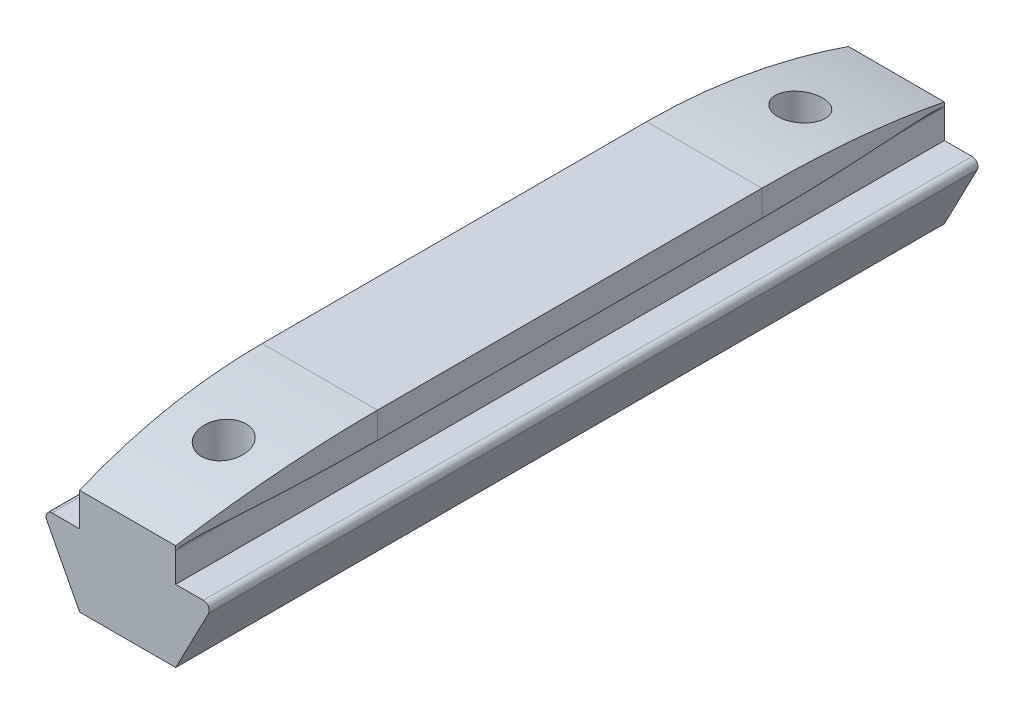
SolidWorks part; units mm, degrees
ref_plane "Front Plane" through (0, 0, 0) normal (0, 0, 1) x (1, 0, 0)
ref_plane "Top Plane" through (0, 0, 0) normal (0, 1, 0) x (1, 0, 0)
ref_plane "Right Plane" through (0, 0, 0) normal (1, 0, 0) x (0, 0, -1)
sketch "Sketch1" plane through (0, 0, 0) normal (0, 0, 1) x (1, 0, 0)
  line L0 (-5.6515, 0) -> (5.6515, 0)
  line L1 (5.6515, 0) -> (3.175, -4.7625)
  line L2 (3.175, -4.7625) -> (-3.175, -4.7625)
  line L3 (0, 0) -> (0, -5.9494) construction
  line L4 (-5.6515, 0) -> (-3.175, -4.7625)
  point P4 (0, -4.7625)
  dimension "D1" = 11.303
  dimension "D2" = 4.7625
  dimension "D3" = 6.35
extrude "Boss-Extrude1" add sketch "Sketch1" along normal mid plane 50.8
sketch "Sketch5" plane through (0, 0, 0) normal (0, 0, 1) x (1, 0, 0)
  line L0 (0, 0) -> (0, 5.1541) construction
  line L1 (5.6515, 0) -> (-5.6515, 0) construction
  line L2 (3.175, 0) -> (3.175, 2.2098)
  line L3 (3.175, 2.2098) -> (3.81, 2.2098)
  line L4 (3.81, 2.2098) -> (3.81, 3.937)
  line L5 (3.81, 3.937) -> (-3.81, 3.937)
  line L6 (3.175, 0) -> (-3.175, 0)
  line L7 (-3.81, 2.2098) -> (-3.81, 3.937)
  line L8 (-3.175, 2.2098) -> (-3.81, 2.2098)
  line L9 (-3.175, 0) -> (-3.175, 2.2098)
  point P11 (0, 3.937)
  dimension "D1" = 6.35
  dimension "D2" = 7.62
  dimension "D3" = 2.2098
  dimension "D4" = 3.937
extrude "Boss-Extrude3" add sketch "Sketch5" along normal mid plane 50.8
fillet "Fillet1" radius 0.3969 2 edges at (-5.6515, 0, 0) (5.6515, 0, 0)
sketch "Sketch3" plane through (0, -4.7625, 0) normal (0, -1, 0) x (1, 0, 0)
  line L2 (-3.175, 25.4) -> (3.175, 25.4) construction
  circle A0 centre (0, 19.05) radius 1.9844
  dimension "D1" = 3.9688
  dimension "D2" = 6.35
sketch "Sketch6" plane through (0, 0, 0) normal (1, 0, 0) x (0, 0, -1)
  line L0 (-25.4, 3.937) -> (25.4, 3.937) construction
  line L1 (0, 5.7817) -> (0, -8.3609) construction
  line L2 (-12.7, 3.937) -> (-25.4, 3.937)
  line L5 (-25.4, 3.937) -> (-25.4, 2.2098)
  arc A0 (-25.4, 2.2098) -> (-12.7, 3.937) centre (-12.7, -43.6178) cw
  dimension "D1" = 25.4
extrude "Cut-Extrude6" cut sketch "Sketch6" against normal up to next and the other way up to next
extrude "Cut-Extrude7" cut sketch "Sketch3" against normal blind 4.7625
sketch "Sketch10" plane through (0, -4.7625, 0) normal (0, -1, 0) x (1, 0, 0)
  circle A0 centre (0, 19.05) radius 2.7686
  dimension "D1" = 5.5372
extrude "Cut-Extrude8" cut sketch "Sketch10" against normal blind 0.508
mirror "Mirror2" about plane through (0, 0, 0) normal (0, 0, 1) of "Cut-Extrude8", "Cut-Extrude6", "Cut-Extrude7"
hole_wizard "#4 Clearance Hole1" positions "Sketch9" profile "Sketch8" hole size "#4" standard "Ansi Inch" end condition up to next
sketch "Sketch9" plane through (0, 0, 0) normal (0, -1, 0) x (1, 0, 0)
  point P0 (0, 19.05)
  point P1 (0, -19.05)
sketch "Sketch8" plane through (0, 0, 19.05) normal (1, 0, 0) x (0, 0, -1)
  line L0 (0, 0) -> (0, 3.5111)
  line L1 (0, 3.5111) -> (1.4732, 3.5111)
  line L2 (1.4732, 3.5111) -> (1.4732, 0)
  line L5 (1.4732, 0) -> (0, 0)
  line L11 (0, -6.35) -> (0, 107.95) construction
  dimension "Thru Hole Dia." = 2.9464
  dimension "Thru Hole Depth" = 3.5111
sketch "Sketch11" plane through (0, 3.937, 0) normal (0, 1, 0) x (1, 0, 0)
  line L0 (-3.81, -12.7) -> (-3.81, 12.7) construction
  line L1 (-3.81, -12.7) -> (-3.81, -25.4)
  line L2 (-3.81, -25.4) -> (-3.175, -25.4)
  arc A0 (-3.81, -12.7) -> (-3.175, -25.4) centre (123.5075, -12.7) ccw
extrude "Cut-Extrude9" cut sketch "Sketch11" against normal up to surface (3.937 mm away) up to face at (-3.6307, 0, 6.35)
mirror "Mirror3" about plane through (0, 0, 0) normal (1, 0, 0) of "Cut-Extrude9"
mirror "Mirror4" about plane through (0, 0, 0) normal (0, 0, 1) of "Cut-Extrude9", "Mirror3"
fillet "Fillet3" radius 0.3175 2 edges at (-3.175, 2.2098, 0) (3.175, 2.2098, 0)
